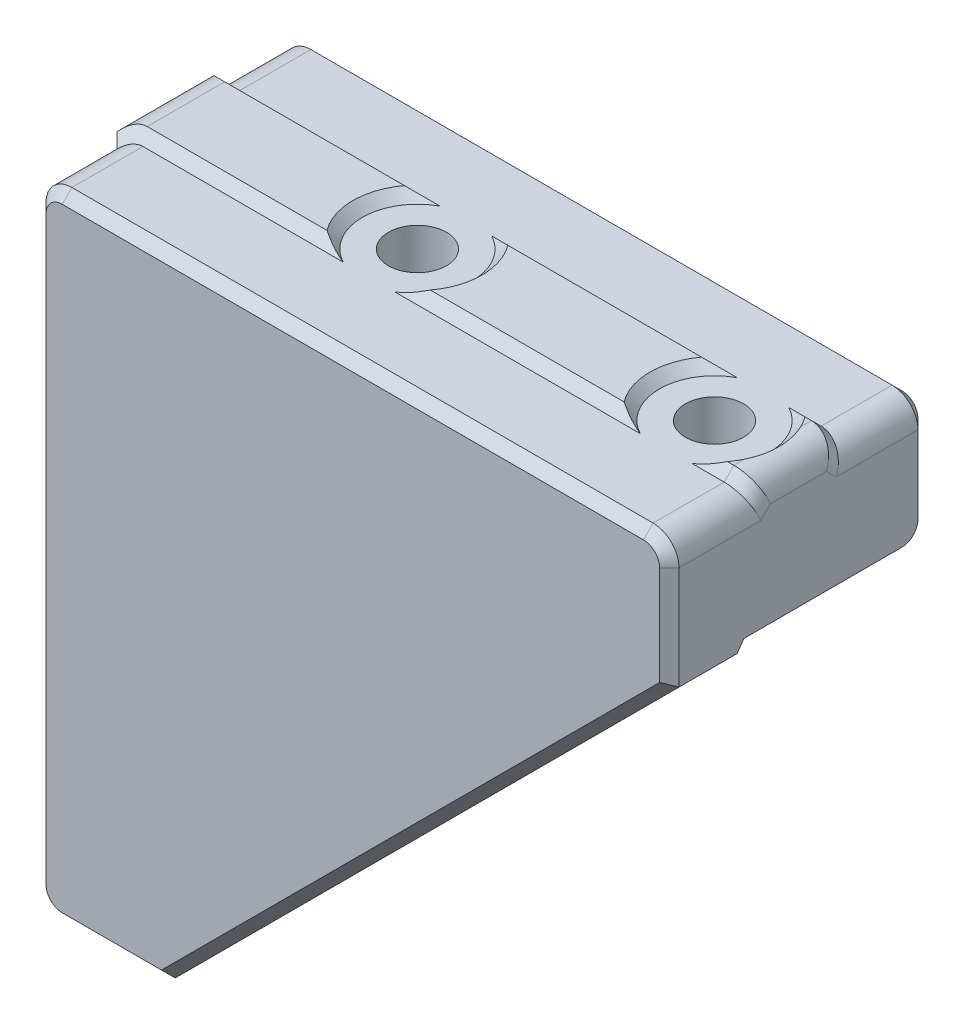
SolidWorks part; units mm, degrees
ref_plane "Front" through (0, 0, 0) normal (0, 0, 1) x (1, 0, 0)
ref_plane "Top" through (0, 0, 0) normal (0, 1, 0) x (1, 0, 0)
ref_plane "Right" through (0, 0, 0) normal (1, 0, 0) x (0, 0, -1)
sketch "Skizze1" plane through (0, 0, 0) normal (0, 0, 1) x (1, 0, 0)
  line L0 (0, 0) -> (0, -39)
  line L1 (0, 0) -> (39, 0)
  line L2 (39, 0) -> (39, 10)
  line L3 (39, 10) -> (-10, 10)
  line L4 (-10, 10) -> (-10, -39)
  line L5 (-10, -39) -> (0, -39)
  dimension "D1" = 49
  dimension "D2" = 10
extrude "Aufsatz-Linear austragen1" add sketch "Skizze1" along normal blind 20
ref_plane "Ebene1" through (0, 0, 0) normal (0.7071, 0.7071, 0) x (0.7071, -0.7071, 0)
sketch "Skizze4" plane through (39, 0, 0) normal (1, 0, 0) x (0, 0, -1)
  line L0 (-10, 10) -> (-10, 19.956) construction
  line L1 (-20, 10) -> (0, 10) construction
  line L2 (-6.25, 10) -> (-7, 10.75)
  line L3 (-7, 10.75) -> (-13, 10.75)
  line L4 (-13.75, 10) -> (-6.25, 10)
  line L5 (-13.75, 10) -> (-13, 10.75)
  point P9 (-10, 10.75)
  dimension "D1" = 7.5
  dimension "D2" = 0.75
  dimension "D3" = 45
extrude "Aufsatz-Linear austragen2" add sketch "Skizze4" against normal up to vertex (49 mm away) up to point (-10, 10, 20)
mirror "Spiegeln3" about plane through (0, 0, 0) normal (0.7071, 0.7071, 0) of "Aufsatz-Linear austragen2"
chamfer "Fase1" distance 0.75 angle 45 2 edges at (-10.75, 10, 10) (-10, 10.75, 10)
sketch "Skizze2" plane through (0, 0, 0) normal (0, -1, 0) x (1, 0, 0)
  line L0 (0, 10) -> (39, 10) construction
  line L1 (0, 20) -> (0, 0) construction
  line L2 (39, 20) -> (39, 0) construction
  circle A0 centre (32.5, 10) radius 2.25
  circle A1 centre (9.5, 10) radius 2.25
  dimension "D1" = 4.5
  dimension "D2" = 6.5
  dimension "D3" = 9.5
extrude "Schnitt-Linear austragen1" cut sketch "Skizze2" against normal blind 20
mirror "Spiegeln4" about plane through (0, 0, 0) normal (0.7071, 0.7071, 0) of "Schnitt-Linear austragen1"
sketch "Skizze5" plane through (0, 0, 20) normal (0, 0, 1) x (1, 0, 0)
  line L0 (0, -39) -> (39, 0)
  line L1 (39, 0) -> (0, 0)
  line L2 (0, 0) -> (0, -39)
extrude "Aufsatz-Linear austragen3" add sketch "Skizze5" against normal blind 6
chamfer "Fase2" distance 5 angle 45 1 edges at (0, 0, 7)
fillet "Verrundung1" radius 2 14 edges at (-10.75, 9.25, 10) (-9.25, 10.75, 10) (-10, 10, 16.875) (-10, 10, 3.125) (-10.375, -39, 13.375) (-10.375, -39, 6.625) (-10.75, -39, 10) (-10, -39, 3.125) (-10, -39, 16.875) (39, 10.375, 13.375) (39, 10.375, 6.625) (39, 10, 16.875) (39, 10.75, 10) (39, 10, 3.125)
fillet "Verrundung2" radius 2 3 edges at (2.5, -2.5, 0) (0, -22, 0) (22, 0, 0)
chamfer "Fase5" distance 0.75 angle 45 19 edges at (39, 0, 8) (19.5, -19.5, 20) (-4, -39, 20) (-9.4142, -38.4142, 20) (39, 4, 20) (-10, -14.5, 20) (38.4142, 9.4142, 20) (-9.4142, 9.4142, 20) (14.5, 10, 20) (0, -39, 8) (-0.5858, -39, 0.5858) (-5, -39, 0) (39, 0.5858, 0.5858) (-9.4142, -38.4142, 0) (39, 5, 0) (-10, -14.5, 0) (38.4142, 9.4142, 0) (-9.4142, 9.4142, 0) (14.5, 10, 0)
chamfer "Fase6" distance 0.75 angle 45 1 edges at (19.5, -19.5, 14)
chamfer "Fase3" distance 1 angle 45 3 edges at (21.4697, 0, 14) (2.5, -2.5, 14) (0, -21.4697, 14)
sketch "Skizze6" plane through (0, 10, 0) normal (0, 1, 0) x (1, 0, 0)
  circle A0 centre (32.5, -10) radius 4
  circle A1 centre (9.5, -10) radius 4
  dimension "D1" = 8
extrude "Schnitt-Linear austragen2" cut sketch "Skizze6" along normal blind 10
sketch "Skizze8" plane through (-10, 0, 0) normal (-1, 0, 0) x (0, 0, 1)
  circle A0 centre (10, -32.5) radius 4
  circle A1 centre (10, -9.5) radius 4
  dimension "D1" = 8
extrude "Schnitt-Linear austragen3" cut sketch "Skizze8" along normal blind 10
chamfer "Fase4" distance 1 angle 45 8 edges at (36.5, 10.75, 10) (28.5, 10.75, 10) (-10.75, -36.5, 10) (-10.75, -28.5, 10) (-10.75, -13.5, 10) (-10.75, -5.5, 10) (13.5, 10.75, 10) (5.5, 10.75, 10)
sketch "Skizze9" plane through (0, 0, 0) normal (0, -1, 0) x (1, 0, 0)
  circle A0 centre (32.5, 10) radius 3.75
  circle A1 centre (9.5, 10) radius 3.75
  dimension "D1" = 7.5
extrude "Schnitt-Linear austragen4" cut sketch "Skizze9" along normal blind 10 and the other way blind 3
mirror "Spiegeln6" about plane through (0, 0, 0) normal (0.7071, 0.7071, 0) of "Schnitt-Linear austragen4"
chamfer "Fase7" distance 1.5 angle 45 4 edges at (32.5, 0, 6.25) (9.5, 0, 6.25) (0, -9.5, 6.25) (0, -32.5, 6.25)
